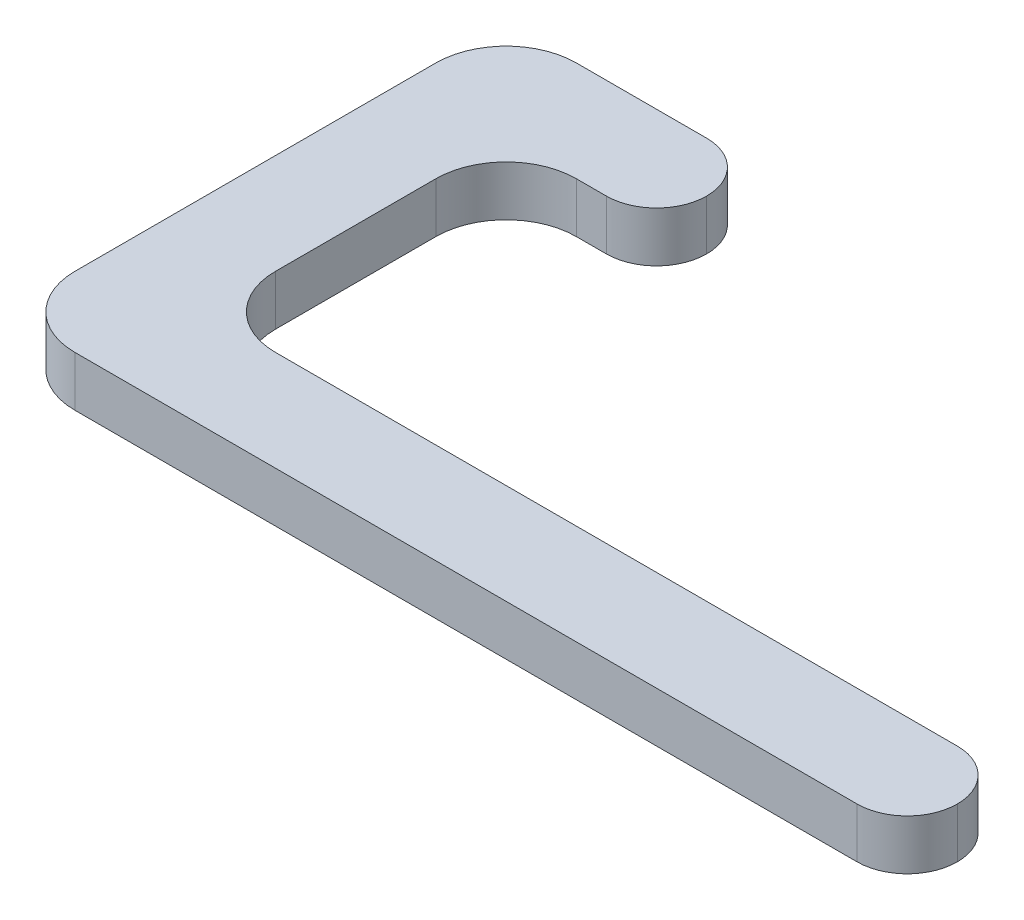
SolidWorks part; units mm, degrees
ref_plane "Front Plane" through (0, 0, 0) normal (0, 0, 1) x (1, 0, 0)
ref_plane "Top Plane" through (0, 0, 0) normal (0, 1, 0) x (1, 0, 0)
ref_plane "Right Plane" through (0, 0, 0) normal (1, 0, 0) x (0, 0, -1)
sketch "Sketch1" plane through (0, 0, 0) normal (0, 1, 0) x (1, 0, 0)
  line L0 (0, 0) -> (0, 15)
  line L1 (0, 15) -> (7.5, 15)
  line L2 (0, 0) -> (40, 0)
  dimension "D1" = 40
  dimension "D2" = 15
  dimension "D3" = 7.5
extrude "Extrude-Thin1" add sketch "Sketch1" along normal blind 2.5 thin thin type one direction wall 5
fillet "Fillet1" radius 2.5 4 edges at (40, 1.25, 5) (40, 1.25, 0) (7.5, 1.25, -15) (7.5, 1.25, -20)
fillet "Fillet2" radius 3.5 4 edges at (0, 1.25, 0) (-5, 1.25, 5) (-5, 1.25, -20) (0, 1.25, -15)
